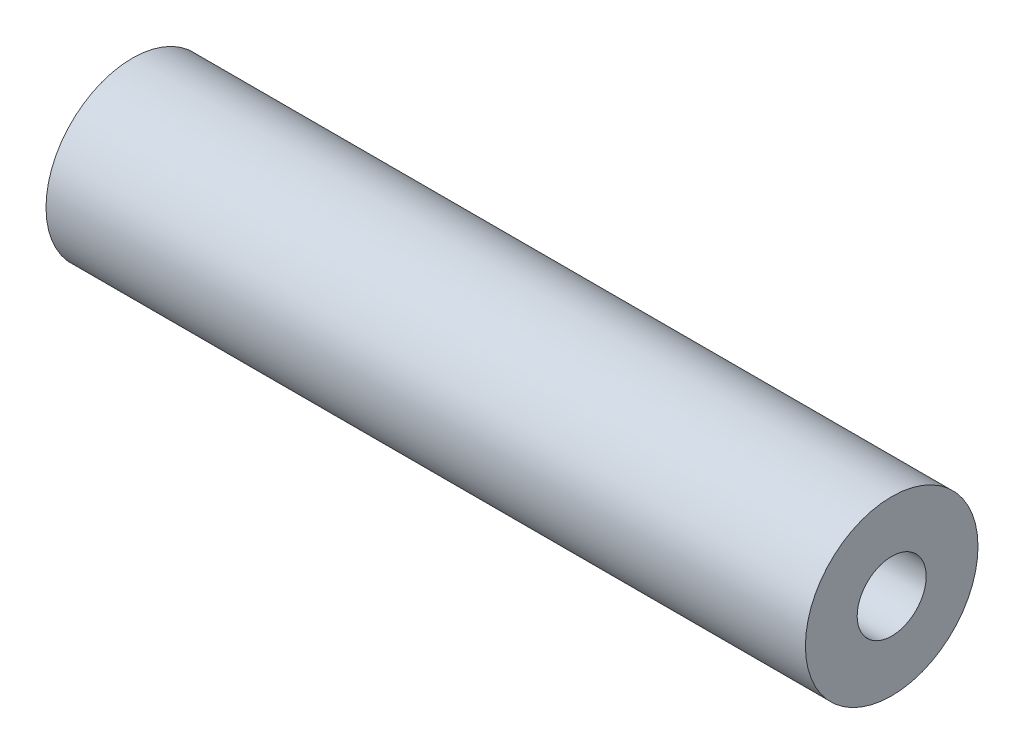
SolidWorks part; units mm, degrees
ref_plane "Front Plane" through (0, 0, 0) normal (0, 0, 1) x (1, 0, 0)
ref_plane "Top Plane" through (0, 0, 0) normal (0, 1, 0) x (1, 0, 0)
ref_plane "Right Plane" through (0, 0, 0) normal (1, 0, 0) x (0, 0, -1)
sketch "Sketch1" plane through (0, 0, 0) normal (0, 0, 1) x (1, 0, 0)
  line L0 (0, 0) -> (150, 0) construction
  line L1 (20, 5) -> (130, 5)
  line L6 (20, 12.5) -> (130, 12.5)
  line L7 (20, 12.5) -> (20, 5)
  line L9 (130, 12.5) -> (130, 5)
  dimension "L" = 150
  dimension "D_s" = 10
  dimension "D" = 25
revolve "Revolve1" add sketch "Sketch1" angle 360 about L0
